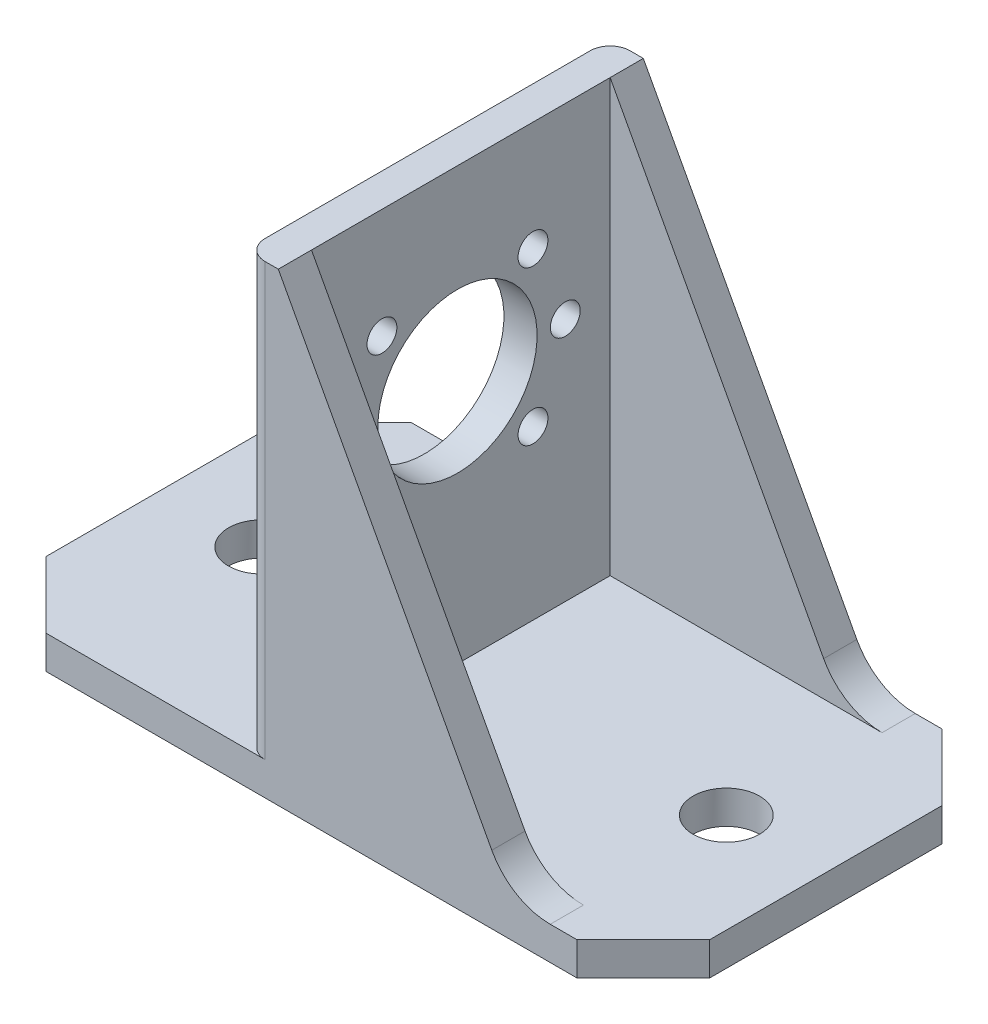
SolidWorks part; units mm, degrees
ref_plane "Alzado" through (0, 0, 0) normal (0, 0, 1) x (1, 0, 0)
ref_plane "Planta" through (0, 0, 0) normal (0, 1, 0) x (1, 0, 0)
ref_plane "Vista lateral" through (0, 0, 0) normal (1, 0, 0) x (0, 0, -1)
sketch "Croquis1" plane through (0, 0, 0) normal (0, 1, 0) x (1, 0, 0)
  line L1 (-50, -27.5) -> (50, -27.5)
  line L2 (-50, -27.5) -> (-50, 27.5)
  line L3 (-50, 27.5) -> (50, 27.5)
  line L4 (50, -27.5) -> (50, 27.5)
  line L5 (-50, -27.5) -> (50, 27.5) construction
  line L6 (-50, 27.5) -> (50, -27.5) construction
  point P0 (0, 0)
  dimension "D1" = 55
  dimension "D2" = 100
extrude "Saliente-Extruir1" add sketch "Croquis1" along normal blind 5
sketch "Croquis2" plane through (0, 5, 0) normal (0, 1, 0) x (1, 0, 0)
  line L0 (0, 27.5) -> (0, -27.5) construction
  line L1 (50, 27.5) -> (-50, 27.5) construction
  line L2 (-50, -27.5) -> (50, -27.5) construction
  line L3 (-35, 0) -> (35, 0) construction
  circle A0 centre (35, 0) radius 5
  circle A1 centre (-35, 0) radius 5
  point P9 (0, 0)
  dimension "D1" = 10
  dimension "D2" = 70
extrude "Cortar-Extruir1" cut sketch "Croquis2" against normal up to surface (5 mm away) up to face at (0, 0, 0)
sketch "Croquis3" plane through (0, 5, 0) normal (0, 1, 0) x (1, 0, 0)
  line L0 (30, 27.5) -> (-7, 27.5)
  line L1 (50, 27.5) -> (-50, 27.5) construction
  line L2 (-10, 24.5) -> (-10, -24.5)
  line L3 (-50, -27.5) -> (50, -27.5) construction
  line L4 (-7, -27.5) -> (30, -27.5)
  line L5 (30, 22.5) -> (-5, 22.5)
  line L6 (-5, 22.5) -> (-5, -22.5)
  line L7 (-5, -22.5) -> (30, -22.5)
  line L8 (30, 27.5) -> (30, 22.5)
  line L9 (30, -22.5) -> (30, -27.5)
  arc A0 (-10, -24.5) -> (-7, -27.5) centre (-7, -24.5) ccw
  arc A1 (-7, 27.5) -> (-10, 24.5) centre (-7, 24.5) ccw
  arc A2 (-5, 22.5) -> (-5, 22.5) centre (-5, 22.5) ccw
  arc A3 (-5, -22.5) -> (-5, -22.5) centre (-5, -22.5) ccw
  point P9 (0, 0)
  point P12 (-10, -27.5)
  point P15 (-10, 27.5)
  dimension "D3" = 3
  dimension "D1" = 40
  dimension "D2" = 10
  dimension "D4" = 5
extrude "Saliente-Extruir2" add sketch "Croquis3" along normal blind 65
sketch "Croquis4" plane through (0, 0, 27.5) normal (0, 0, 1) x (1, 0, 0)
  line L0 (-5, 70) -> (-5, 5) construction
  line L1 (-5, 70) -> (-5, 5) construction
  line L2 (-5, 70) -> (30, 5)
  line L3 (30, 5) -> (30, 70)
  line L4 (30, 70) -> (-5, 70)
extrude "Cortar-Extruir2" cut sketch "Croquis4" against normal up to surface (55 mm away) up to face at (5.75, 20, -27.5)
chamfer "Chaflán1" distance 10 angle 45 4 edges at (50, 2.5, 27.5) (50, 2.5, -27.5) (-50, 2.5, -27.5) (-50, 2.5, 27.5)
fillet "Redondeo1" radius 10 2 edges at (30, 5, 25) (30, 5, -25)
sketch "Croquis5" plane through (-10, 0, 0) normal (-1, 0, 0) x (0, 0, 1)
  circle A0 centre (0.5053, 41.8683) radius 12 construction
  circle A1 centre (0.5053, 41.8683) radius 12
  circle A2 centre (-15.7447, 41.8683) radius 2.25 construction
  circle A3 centre (-15.7447, 41.8683) radius 2.25 construction
  circle A4 centre (-10.8746, 30.2683) radius 2.25 construction
  circle A5 centre (11.8852, 30.2683) radius 2.25 construction
  circle A6 centre (16.7553, 41.8683) radius 2.25 construction
  circle A7 centre (11.8852, 53.4683) radius 2.25 construction
  circle A8 centre (-15.7447, 41.8683) radius 2.25
  circle A9 centre (-15.7447, 41.8683) radius 2.25
  circle A10 centre (-10.8746, 30.2683) radius 2.25
  circle A11 centre (11.8852, 30.2683) radius 2.25
  circle A12 centre (16.7553, 41.8683) radius 2.25
  circle A13 centre (11.8852, 53.4683) radius 2.25
  circle A14 centre (-10.8746, 53.4683) radius 2.25 construction
  circle A15 centre (-10.8746, 53.4683) radius 2.25
extrude "Cortar-Extruir3" cut sketch "Croquis5" against normal up to surface (5 mm away) contours A1 | A11 | A12 | A13 | A10 | A8 | A15 region at (-10, 41.8683, 0.5053) region at (-10, 41.8683, -15.7447) region at (-10, 30.2683, -10.8746) region at (-10, 30.2683, 11.8852) region at (-10, 41.8683, 16.7553) region at (-10, 53.4683, 11.8852) region at (-10, 53.4683, -10.8746) up to face at (-5, 37.5, 0)
